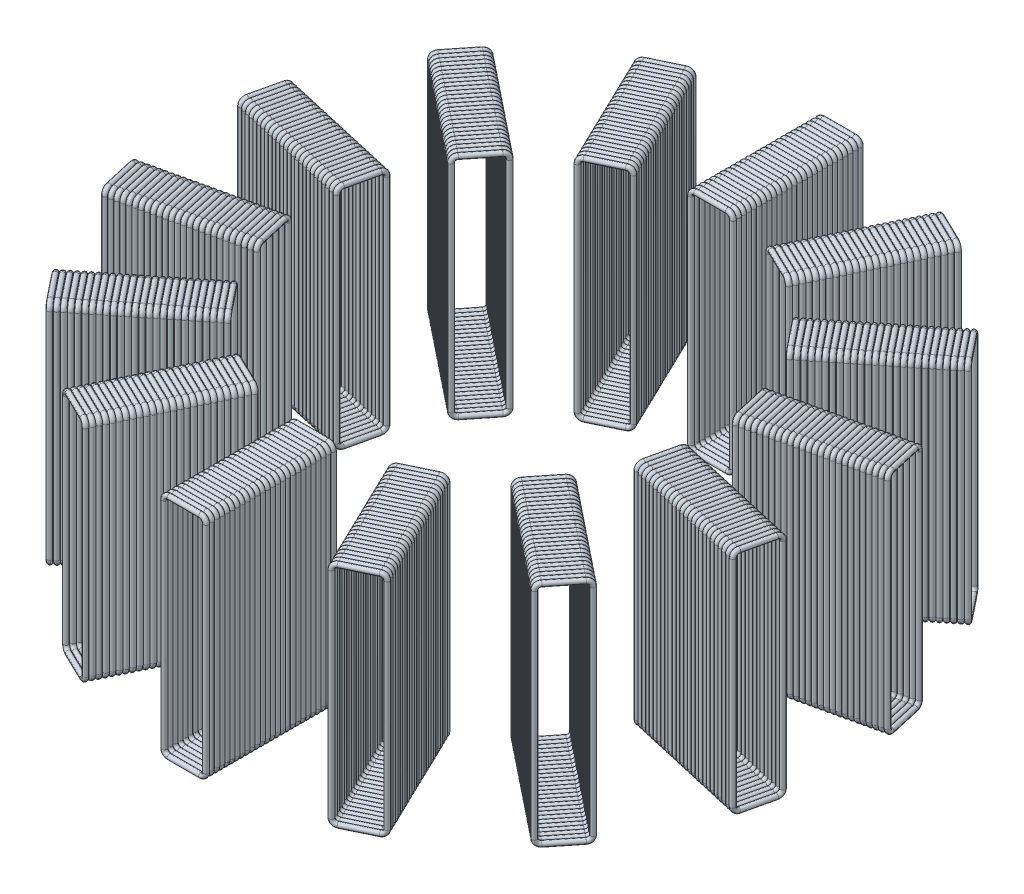
SolidWorks part; units mm, degrees
ref_plane "Front Plane" through (0, 0, 0) normal (0, 0, 1) x (1, 0, 0)
ref_plane "Top Plane" through (0, 0, 0) normal (0, 1, 0) x (1, 0, 0)
ref_plane "Right Plane" through (0, 0, 0) normal (1, 0, 0) x (0, 0, -1)
sketch "Эскиз1" plane through (0, 0, 0) normal (0, 0, 1) x (1, 0, 0)
  line L1 (-0.625, -4.45) -> (0.625, -4.45)
  line L2 (-0.825, -4.25) -> (-0.825, 4.25)
  line L3 (-0.625, 4.45) -> (0.625, 4.45)
  line L4 (0.825, -4.25) -> (0.825, 4.25)
  line L5 (-0.825, -4.45) -> (0.825, 4.45) construction
  line L6 (-0.825, 4.45) -> (0.825, -4.45) construction
  arc A0 (0.625, -4.45) -> (0.825, -4.25) centre (0.625, -4.25) ccw
  arc A1 (-0.625, -4.45) -> (-0.825, -4.25) centre (-0.625, -4.25) cw
  arc A2 (0.625, 4.45) -> (0.825, 4.25) centre (0.625, 4.25) cw
  arc A3 (-0.825, 4.25) -> (-0.625, 4.45) centre (-0.625, 4.25) cw
  point P0 (0, 0)
  dimension "D3" = 0.2
  dimension "D1" = 8.9
  dimension "D2" = 1.65
sweep "По траектории1" add path "Эскиз1" circular profile diameter 0.2 parameters "D3"=0.2
pattern_linear "Линейный массив2" count 26 spacing 0.2 along (0, 0, 1) of bodies 101
sketch "Эскиз3" plane through (0, 0, 0) normal (0, 1, 0) x (1, 0, 0)
  line L0 (0, 0) -> (0, 7.9) construction
  circle A0 centre (0, 7.9) radius 7.9
  dimension "D1" = 7.9
surface "Поверхность-Заполнить1" sketch "Эскиз3"
pattern_circular "Круговой массив1" count 14 over 360 about axis through (0, 0, -7.9) along (0, 1, 0)
